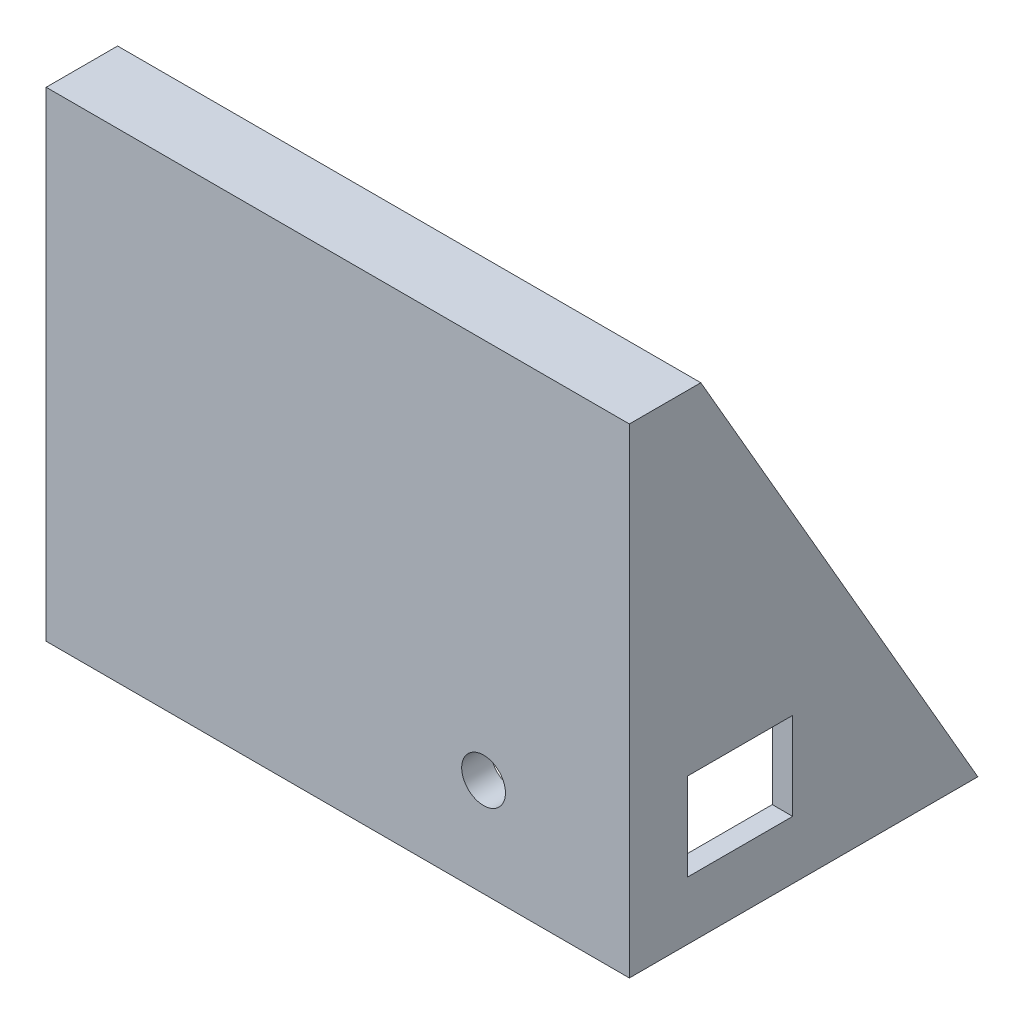
SolidWorks part; units mm, degrees
material "ABS"
ref_plane "Front Plane" through (0, 0, 0) normal (0, 0, 1) x (1, 0, 0)
ref_plane "Top Plane" through (0, 0, 0) normal (0, 1, 0) x (1, 0, 0)
ref_plane "Right Plane" through (0, 0, 0) normal (1, 0, 0) x (0, 0, -1)
sketch "Sketch2" plane through (0, 0, 0) normal (1, 0, 0) x (0, 0, -1)
  line L0 (0, 60.7895) -> (24.5, 60.7895)
  line L1 (24.5, 60.7895) -> (119.5, -103.7554)
  line L2 (119.5, -103.7554) -> (0, -103.7554)
  line L3 (0, -103.7554) -> (0, 60.7895)
  dimension "D1" = 24.5
  dimension "D2" = 190
  dimension "D3" = 120
extrude "Boss-Extrude1" add sketch "Sketch2" along normal blind 200
shell "Shell1" thickness 10 removed face at (100, -103.7554, -59.75)
sketch "Sketch4" plane through (0, 25.8062, -44.6976) normal (0, 0.5, -0.866) x (-1, 0, 0)
  line L0 (-200, 40.3952) -> (0, 40.3952) construction
  line L1 (-200, -149.6048) -> (-200, 40.3952) construction
  line L3 (0, -149.6048) -> (0, 40.3952) construction
  line L4 (-200, -149.6048) -> (0, -149.6048) construction
  circle A0 centre (-185, 0.3952) radius 2.5
  circle A1 centre (-185, -109.6048) radius 2.5
  circle A2 centre (-155, -139.6048) radius 2.5
  circle A3 centre (-45, -139.6048) radius 2.5
  circle A4 centre (-15, -109.6048) radius 2.5
  circle A5 centre (-15, 0.3952) radius 2.5
  circle A6 centre (-45, 30.3952) radius 2.5
  circle A7 centre (-155, 30.3952) radius 2.5
  dimension "D1" = 5
  dimension "D2" = 5
  dimension "D3" = 5
  dimension "D4" = 5
  dimension "D5" = 5
  dimension "D6" = 5
  dimension "D7" = 5
  dimension "D8" = 5
  dimension "D10" = 15
  dimension "D11" = 40
  dimension "D12" = 45
  dimension "D13" = 45
  dimension "D14" = 15
  dimension "D15" = 10
  dimension "D16" = 40
  dimension "D17" = 40
  dimension "D18" = 15
  dimension "D19" = 10
  dimension "D20" = 45
  dimension "D21" = 15
  dimension "D22" = 40
  dimension "D23" = 10
  dimension "D24" = 45
  dimension "D9" = 10
extrude "Cut-Extrude2" cut sketch "Sketch4" against normal blind 5
sketch "Sketch5" plane through (200, 0, 0) normal (1, 0, 0) x (0, 0, -1)
  line L0 (0, 60.7895) -> (0, -103.7554) construction
  line L1 (20, -53.7554) -> (56, -53.7554)
  line L2 (20, -53.7554) -> (20, -83.7554)
  line L3 (20, -83.7554) -> (56, -83.7554)
  line L4 (56, -53.7554) -> (56, -83.7554)
  line L5 (0, -103.7554) -> (119.5, -103.7554) construction
  point P6 (20, -68.7554)
  dimension "D1" = 36
  dimension "D2" = 30
  dimension "D3" = 20
  dimension "D4" = 20
extrude "Cut-Extrude3" cut sketch "Sketch5" against normal blind 20
sketch "Sketch6" plane through (0, 0, 0) normal (0, 0, 1) x (1, 0, 0)
  line L0 (200, 60.7895) -> (200, -103.7554) construction
  circle A0 centre (150, -70.0359) radius 7.5
  dimension "D1" = 15
  dimension "D2" = 50
extrude "Cut-Extrude4" cut sketch "Sketch6" against normal blind 20
sketch "Sketch7" plane through (0, 0, 0) normal (0, 0, 1) x (1, 0, 0)
  line L0 (200, -103.7554) -> (0, -103.7554) construction
  line L1 (0, 60.7895) -> (200, 60.7895)
  line L2 (0, 60.7895) -> (0, -103.7554)
  line L3 (0, -103.7554) -> (200, -103.7554)
  line L4 (200, 60.7895) -> (200, -103.7554)
extrude "Boss-Extrude2" [suppressed] add sketch "Sketch7" along normal blind 60
sketch "Sketch8" plane through (0, 0, -10) normal (0, 0, -1) x (-1, 0, 0)
  circle A0 centre (-150, -70.0359) radius 7.5
extrude "Cut-Extrude5" [suppressed] cut sketch "Sketch8" against normal through all
sketch "Sketch14" plane through (0, 60.7895, 0) normal (0, 1, 0) x (1, 0, 0)
  line L0 (0, -60) -> (-6.1272, -62.0017)
  line L1 (-6.1272, -62.0017) -> (0, -51.8189)
  line L2 (200, -60) -> (206.2634, -60)
  line L3 (206.2634, -60) -> (203.6169, -51.899)
  line L4 (203.6169, -51.899) -> (200, -51.899)
  line L8 (0, -51.8189) -> (0, -60)
  line L9 (0, -60) -> (200, -60)
  line L10 (200, -60) -> (200, -51.899)
  spline S2 degree 3 poles (200, -51.899) (198.8085, -50.8812) (197.5963, -49.8841) (194.763, -47.639) (193.1253, -46.4034) (188.1518, -42.829) (184.7446, -40.6125) (177.7611, -36.4874) (174.1845, -34.5791) (166.8707, -31.0548) (163.134, -29.4377) (157.4116, -27.2257) (155.4927, -26.5272) (151.6403, -25.2084) (149.7056, -24.5876) (143.8764, -22.8379) (139.957, -21.8218) (132.0538, -20.0801) (128.07, -19.3547) (122.0464, -18.483) (120.0305, -18.2286) (115.9827, -17.7924) (113.9494, -17.6105) (107.8336, -17.1755) (103.7701, -17.0354) (91.619, -17.0522) (83.571, -17.6433) (71.578, -19.3991) (67.5936, -20.1303) (61.6376, -21.4536) (59.6557, -21.9326) (55.699, -22.9683) (53.737, -23.5218) (47.9015, -25.2879) (44.0776, -26.6062) (36.5638, -29.5265) (32.8738, -31.1287) (25.6323, -34.6265) (22.0813, -36.5233) (15.1288, -40.6338) (11.7272, -42.8472) (7.5776, -45.8312) (6.7517, -46.4398) (5.1169, -47.6744) (4.3082, -48.3002) (2.3195, -49.8771) (1.15, -50.8385) (0, -51.8189) knots 0.222344 0.222344 0.222344 0.222344 0.234375 0.234375 0.25 0.25 0.28125 0.28125 0.3125 0.3125 0.34375 0.34375 0.359375 0.359375 0.375 0.375 0.40625 0.40625 0.4375 0.4375 0.453125 0.453125 0.46875 0.46875 0.5 0.5 0.5625 0.5625 0.59375 0.59375 0.609375 0.609375 0.625 0.625 0.65625 0.65625 0.6875 0.6875 0.71875 0.71875 0.75 0.75 0.757812 0.757812 0.765625 0.765625 0.777234 0.777234 0.777234 0.777234
  line M17 (0, 24.5) -> (0, 0)
  line M19 (200, 0) -> (200, 24.5)
extrude "Cut-Extrude7" [suppressed] cut sketch "Sketch14" against normal through all contours L3 L4 L2 M19 | L10 S2 L9 M17 | L8 L1 L0
sketch "Sketch16" [suppressed] plane through (0, 60.7895, 0) normal (0, 1, 0) x (1, 0, 0)
  line L0 (200, -51.899) -> (217.6123, -51.899)
  line L1 (217.6123, -51.899) -> (217.6123, -73.519)
  line L2 (217.6123, -73.519) -> (206.6918, -73.519)
  line L3 (-9.5151, -73.519) -> (-9.5151, -51.899)
  line L4 (-9.5151, -51.899) -> (200, -51.899)
  line L5 (206.6918, -73.519) -> (-9.5151, -73.519)
extrude "Cut-Extrude8" [suppressed] cut sketch "Sketch16" against normal through all
